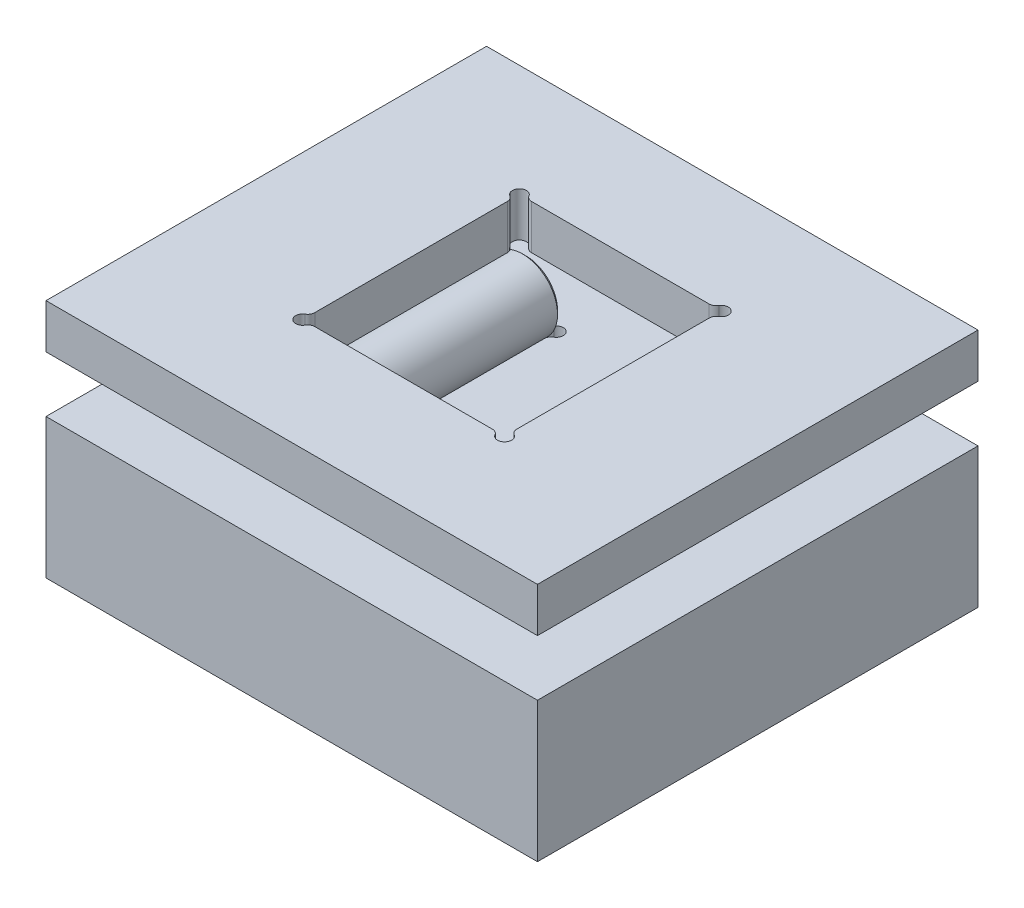
SolidWorks part; units mm, degrees
ref_plane "Front Plane" through (0, 0, 0) normal (0, 0, 1) x (1, 0, 0)
ref_plane "Top Plane" through (0, 0, 0) normal (0, 1, 0) x (1, 0, 0)
ref_plane "Right Plane" through (0, 0, 0) normal (1, 0, 0) x (0, 0, -1)
sketch "Sketch1" plane through (0, 0, 0) normal (0, 0, 1) x (1, 0, 0)
  line L0 (-6.4952, -3.75) -> (6.4952, -3.75) construction
  line L5 (-6.4952, -3.75) -> (0, 0) construction
  line L6 (-6.4952, -3.75) -> (-4.5801, -5.357) construction
  line L11 (-4.5801, -5.357) -> (4.5801, -5.357)
  line L12 (4.5801, -5.357) -> (4.5801, -15.357)
  line L13 (4.5801, -15.357) -> (-4.5801, -15.357)
  line L14 (-4.5801, -15.357) -> (-4.5801, -5.357)
  line L15 (-8.4103, -5.357) -> (-8.4103, -15.357)
  line L16 (-8.4103, -15.357) -> (-17.5705, -15.357)
  line L17 (-17.5705, -15.357) -> (-17.5705, -5.357)
  line L18 (-17.5705, -5.357) -> (-8.4103, -5.357)
  line L19 (0, -5.357) -> (0, -15.357) construction
  line L20 (17.5705, -5.357) -> (8.4103, -5.357)
  line L21 (8.4103, -15.357) -> (17.5705, -15.357)
  line L22 (8.4103, -5.357) -> (8.4103, -15.357)
  line L23 (17.5705, -15.357) -> (17.5705, -5.357)
  line L24 (-7.2187, -1.357) -> (-17.5705, -1.357)
  line L25 (-6.4952, -3.75) -> (-7.2187, -1.357) construction
  line L26 (-17.5705, -1.357) -> (-17.5705, 1.818)
  line L27 (-17.5705, 1.818) -> (-7.2187, 1.818)
  line L28 (-7.2187, 1.818) -> (-7.2187, -1.357)
  line L29 (17.5705, 1.818) -> (7.2187, 1.818)
  line L30 (17.5705, -1.357) -> (17.5705, 1.818)
  line L31 (7.2187, -1.357) -> (17.5705, -1.357)
  line L32 (7.2187, 1.818) -> (7.2187, -1.357)
  circle A1 centre (0, 0) radius 5
  circle A2 centre (6.4952, -3.75) radius 2.5
  circle A3 centre (-6.4952, -3.75) radius 2.5
  point P21 (0, -5)
  dimension "D1" = 10
  dimension "D2" = 5
  dimension "D3" = 30
  dimension "D4" = 40
  dimension "D5" = 10
  dimension "D6" = 4
  dimension "D7" = 3.175
extrude "Boss-Extrude1" add sketch "Sketch1" along normal blind 7.75 contours L14 L13 L12 L11 | L21 L23 L20 L22 | L18 L15 L16 L17 | L28 L24 L26 L27 | L29 L32 L31 L30 region at (0, -10.357, 0) region at (12.9904, -10.357, 0)
sketch "Sketch2" plane through (0, 0, 7.75) normal (0, 0, 1) x (1, 0, 0)
  line L1 (-17.5705, -5.357) -> (17.5705, -5.357)
  line L2 (-17.5705, -5.357) -> (-17.5705, -15.357)
  line L3 (-17.5705, -15.357) -> (17.5705, -15.357)
  line L4 (17.5705, -5.357) -> (17.5705, -15.357)
  line L5 (-17.5705, -1.357) -> (17.5705, -1.357)
  line L6 (-17.5705, -1.357) -> (-17.5705, 1.818)
  line L7 (-17.5705, 1.818) -> (17.5705, 1.818)
  line L8 (17.5705, -1.357) -> (17.5705, 1.818)
extrude "Boss-Extrude2" add sketch "Sketch2" along normal blind 8
sketch "Sketch3" plane through (0, -5.357, 0) normal (0, 1, 0) x (1, 0, 0)
  circle A0 centre (-8.4103, -7.75) radius 0.5
  circle A1 centre (-4.5801, -7.75) radius 0.5
  circle A2 centre (4.5801, -7.75) radius 0.5
  circle A3 centre (8.4103, -7.75) radius 0.5
  dimension "D1" = 1
extrude "Cut-Extrude1" cut sketch "Sketch3" against normal through all
sketch "Sketch4" plane through (0, 1.818, 0) normal (0, 1, 0) x (1, 0, 0)
  circle A0 centre (-7.2187, -7.75) radius 0.5
  circle A1 centre (7.2187, -7.75) radius 0.5
  arc A2 (-5.0801, -7.75) -> (-4.5801, -7.25) centre (-4.5801, -7.75) ccw construction
extrude "Cut-Extrude2" cut sketch "Sketch4" against normal up to surface (3.175 mm away) up to face at (0, -1.357, 5.875)
fillet "Fillet1" radius 0.5 8 edges at (4.5801, -10.357, 7.25) (8.4103, -10.357, 7.25) (7.9103, -10.357, 7.75) (5.0801, -10.357, 7.75) (-4.5801, -10.357, 7.25) (-5.0801, -10.357, 7.75) (-7.9103, -10.357, 7.75) (-8.4103, -10.357, 7.25)
fillet "Fillet2" radius 0.5 4 edges at (7.2187, 0.2305, 7.25) (6.7187, 0.2305, 7.75) (-7.2187, 0.2305, 7.25) (-6.7187, 0.2305, 7.75)
mirror "Mirror1" about plane through (0, 0, 0) normal (0, 0, -1) of bodies 105 112
extrude "Boss-Extrude3" add sketch "Sketch1<3>" along normal mid plane 15 separate body contours A2 | A3 region at (6.4952, -3.75, 0)
sketch "Sketch1<3>" plane through (0, 0, 0) normal (0, 0, 1) x (1, 0, 0) same geometry as "Sketch1"
chamfer "Chamfer1" distance 0.25 angle 45 2 edges at (-3.9952, -3.75, -7.5) (-3.9952, -3.75, 7.5)
chamfer "Chamfer2" distance 0.25 angle 45 2 edges at (8.9952, -3.75, -7.5) (8.9952, -3.75, 7.5)
